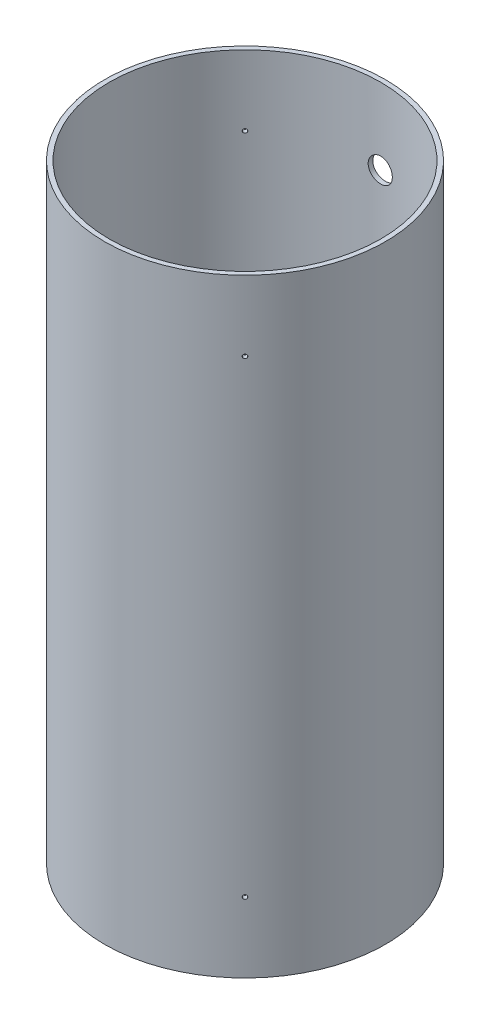
SolidWorks part; units mm, degrees
material "A-Glass Fiber"
ref_plane "Front Plane" through (0, 0, 0) normal (0, 0, 1) x (1, 0, 0)
ref_plane "Top Plane" through (0, 0, 0) normal (0, 1, 0) x (1, 0, 0)
ref_plane "Right Plane" through (0, 0, 0) normal (1, 0, 0) x (0, 0, -1)
sketch "Sketch1" plane through (0, 0, 0) normal (0, 1, 0) x (1, 0, 0)
  circle A0 centre (0, 0) radius 76.1746
  circle A1 centre (0, 0) radius 73.66
  dimension "D1" = 152.3492
  dimension "D2" = 147.32
extrude "Boss-Extrude1" add sketch "Sketch1" along normal blind 330.2
sketch "Sketch4" plane through (0, 0, 0) normal (0, 0, 1) x (1, 0, 0)
  line L0 (-76.1746, 0) -> (76.1746, 0) construction
  line L1 (76.1746, 330.2) -> (-76.1746, 330.2) construction
  line L2 (0, 330.2) -> (0, 0) construction
  line L3 (73.66, 330.2) -> (-73.66, 330.2) construction
  point P0 (0, 41.275)
  point P3 (0, 288.925)
  point P6 (0, 0)
  point P11 (0, 0)
  dimension "D1" = 41.275
  dimension "D2" = 41.275
hole_wizard "1/2 Clearance Hole5" positions "Sketch16" profile "Sketch17" hole size "1/2" standard "ANSI Inch"
sketch "Sketch16" plane through (0, 0, 0) normal (0, 0, 1) x (1, 0, 0)
  point P0 (0, 288.925)
sketch "Sketch17" plane through (0, 288.925, 0) normal (1, 0, 0) x (0, -1, 0)
  line L0 (0, 0) -> (0, 80.1345)
  line L1 (0, 80.1345) -> (6.5481, 76.2)
  line L2 (6.5481, 76.2) -> (6.5481, 0)
  line L5 (6.5481, 0) -> (0, 0)
  line L10 (0, 80.1345) -> (-6.5481, 76.2) construction
  line L11 (0, -6.35) -> (0, 107.95) construction
  dimension "Hole Dia." = 13.0962
  dimension "Hole Depth" = 76.2
  dimension "Drill Angle" = 118
hole_wizard "1/2 Clearance Hole7" positions "Sketch20" profile "Sketch21" hole size "1/2" standard "ANSI Inch"
sketch "Sketch20" plane through (0, 0, 0) normal (0, 0, 1) x (1, 0, 0)
  point P0 (0, 41.275)
sketch "Sketch21" plane through (0, 41.275, 0) normal (1, 0, 0) x (0, -1, 0)
  line L0 (0, 0) -> (0, 80.1345)
  line L1 (0, 80.1345) -> (6.5481, 76.2)
  line L2 (6.5481, 76.2) -> (6.5481, 0)
  line L5 (6.5481, 0) -> (0, 0)
  line L10 (0, 80.1345) -> (-6.5481, 76.2) construction
  line L11 (0, -6.35) -> (0, 107.95) construction
  dimension "Hole Dia." = 13.0962
  dimension "Hole Depth" = 76.2
  dimension "Drill Angle" = 118
ref_plane "Plane1" through (0, 0, 0) normal (-0.7071, 0, 0.7071) x (0.7071, 0, 0.7071)
sketch "Sketch23" plane through (0, 0, 0) normal (-0.7071, 0, 0.7071) x (0.7071, 0, 0.7071)
  line L0 (0, 0) -> (0, 330.2) construction
  line L1 (73.66, 330.2) -> (-73.66, 330.2) construction
  line L2 (-76.1746, 165.1) -> (76.1746, 165.1) construction
  line L3 (76.1746, 0) -> (76.1746, 330.2) construction
  circle A0 centre (0, 292.1) radius 1.0922
  circle A1 centre (0, 38.1) radius 1.0922
  point P11 (-75.9779, 177.3063)
  point P12 (0, 165.1)
  point P13 (121.8137, 165.1)
  point P14 (0, 0)
  point P15 (76.1746, 165.1)
  dimension "D3" = 2.1844
  dimension "D1" = 127
  dimension "D2" = 127
extrude "Shear Scrrews" cut sketch "Sketch23" against normal through all
pattern_circular "CirPattern1" count 4 over 360 about axis through (0, 330.2, 0) along (0, -1, 0) of "Shear Scrrews"
equation "\"Mid_Coupler_Length\" = 13in"
equation "\"D1@Boss-Extrude1\"=\"Mid_Coupler_Length\""
equation "\"Shear_Screw_Coupler_Location\" = 4.5in"
equation "\"D1@Sketch23\"=\"Shear_Screw_Coupler_Location\"+0.5"
equation "\"Shear_Screw_Diameter\" = 0.086in"
equation "\"D2@Sketch23\"=\"Shear_Screw_Coupler_Location\"+0.5"
equation "\"D3@Sketch23\"=\"Shear_Screw_Diameter\""
